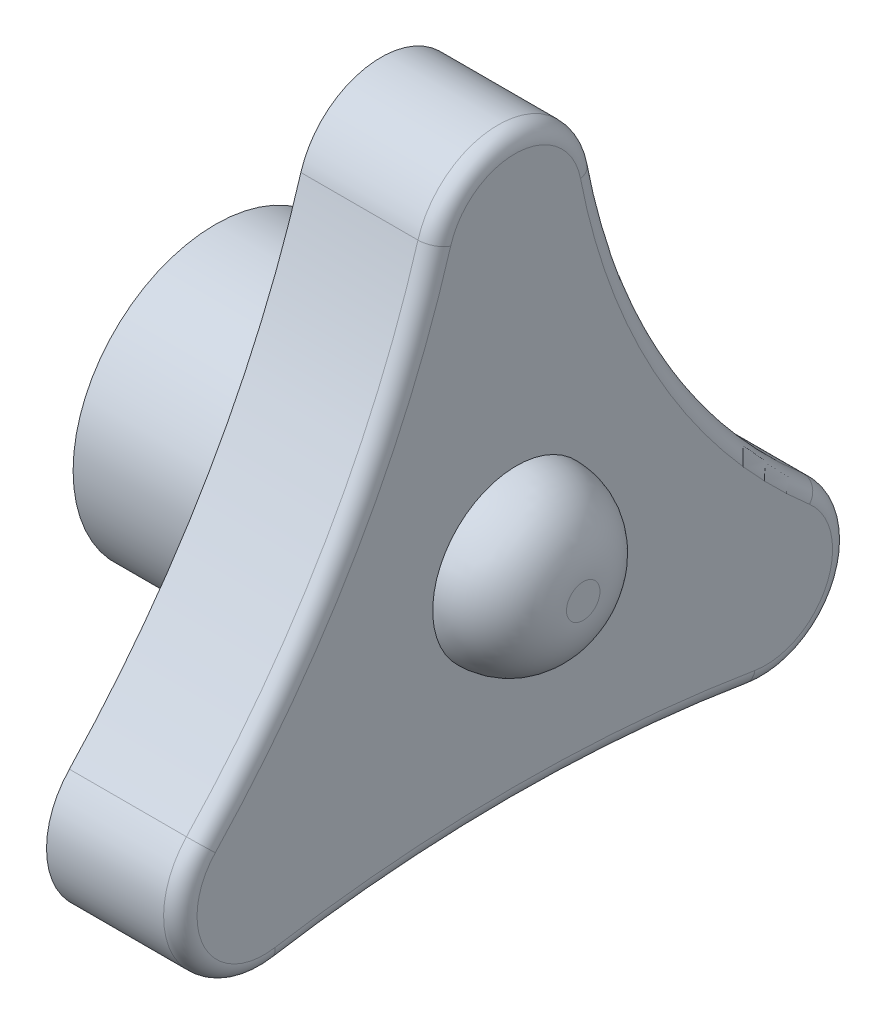
SolidWorks part; units mm, degrees
ref_plane "Front Plane" through (0, 0, 0) normal (0, 0, 1) x (1, 0, 0)
ref_plane "Top Plane" through (0, 0, 0) normal (0, 1, 0) x (1, 0, 0)
ref_plane "Right Plane" through (0, 0, 0) normal (1, 0, 0) x (0, 0, -1)
sketch "Sketch1" plane through (0, 0, 0) normal (1, 0, 0) x (0, 0, -1)
  line L0 (-7.5, 0) -> (7.5, 0) construction
  line L1 (7.5, 0) -> (0, 12.9904) construction
  line L2 (0, 12.9904) -> (-7.5, 0) construction
  arc A0 (2.4549, 13.4629) -> (-2.3958, 13.7048) centre (0, 12.9904) ccw
  arc A1 (-9.3166, 1.7176) -> (-7.0943, -2.4669) centre (-7.5, 0) ccw
  arc A2 (7.0943, -2.4669) -> (9.1367, 1.8898) centre (7.5, 0) ccw
  arc A3 (-9.3166, 1.7176) -> (-2.3958, 13.7048) centre (-31.0222, 22.2408) ccw
  arc A4 (9.1367, 1.8898) -> (2.4549, 13.4629) centre (22.5024, 17.3219) cw
  arc A5 (7.0943, -2.4669) -> (-7.0943, -2.4669) centre (0, -45.6019) ccw
  point P5 (0, 0)
  dimension "D2" = 5
  dimension "D1" = 15
extrude "Boss-Extrude1" add sketch "Sketch1" along normal blind 4
fillet "Fillet1" radius 0.5 6 edges at (4, 15.4873, -0.1245) (4, 7.1141, -4.8221) (4, -1.0612, -9.7636) (4, -1.8874, 0) (4, -1.1726, 9.7079) (4, 7.3048, 5.1523)
shell "Shell2" thickness 1 removed face at (0, 4.2975, 0.025)
sketch "Sketch2" plane through (3, 0, 0) normal (-1, 0, 0) x (0, 0, 1)
  line L0 (-0.1245, 15.4873) -> (0, -1.8874) construction
  line L1 (0, -1.8874) -> (9.7079, -1.1726) construction
  line L2 (9.7079, -1.1726) -> (-4.8221, 7.1141) construction
  line L3 (-4.8221, 7.1141) -> (-9.7636, -1.0612) construction
  line L4 (-9.7636, -1.0612) -> (5.1523, 7.3048) construction
  arc A0 (2.3958, 13.7048) -> (-2.4549, 13.4629) centre (0, 12.9904) ccw construction
  arc A1 (7.0943, -2.4669) -> (-7.0943, -2.4669) centre (0, -45.6019) ccw construction
  arc A2 (7.0943, -2.4669) -> (9.3166, 1.7176) centre (7.5, 0) ccw construction
  arc A3 (-9.1367, 1.8898) -> (-2.4549, 13.4629) centre (-22.5024, 17.3219) ccw construction
  arc A4 (-9.1367, 1.8898) -> (-7.0943, -2.4669) centre (-7.5, 0) ccw construction
  arc A5 (2.3958, 13.7048) -> (9.3166, 1.7176) centre (31.0222, 22.2408) ccw construction
  circle A6 centre (-0.045, 4.3897) radius 2.25
  circle A7 centre (-0.045, 4.3897) radius 4.25
  dimension "D1" = 4.5
  dimension "D2" = 2
extrude "Boss-Extrude2" add sketch "Sketch2" along normal blind 8
sketch "Sketch3" plane through (4, 0, 0) normal (1, 0, 0) x (0, 0, -1)
  line L0 (-5.1523, 7.3048) -> (9.7636, -1.0612) construction
  line L1 (9.7636, -1.0612) -> (4.8221, 7.1141) construction
  line L2 (4.8221, 7.1141) -> (-9.7079, -1.1726) construction
  line L3 (-9.7079, -1.1726) -> (0, -1.8874) construction
  line L4 (0, -1.8874) -> (0.1245, 15.4873) construction
  arc A0 (-9.3166, 1.7176) -> (-2.3958, 13.7048) centre (-31.0222, 22.2408) ccw construction
  arc A1 (7.0943, -2.4669) -> (9.1367, 1.8898) centre (7.5, 0) ccw construction
  arc A2 (2.4549, 13.4629) -> (9.1367, 1.8898) centre (22.5024, 17.3219) ccw construction
  arc A3 (-9.3166, 1.7176) -> (-7.0943, -2.4669) centre (-7.5, 0) ccw construction
  arc A4 (7.0943, -2.4669) -> (-7.0943, -2.4669) centre (0, -45.6019) ccw construction
  arc A5 (2.4549, 13.4629) -> (-2.3958, 13.7048) centre (0, 12.9904) ccw construction
  circle A6 centre (0.045, 4.3898) radius 2.5
  dimension "D1" = 5
extrude "Boss-Extrude3" add sketch "Sketch3" along normal blind 2
fillet "Fillet2" radius 2 1 edges at (6, 4.3898, -2.545)
